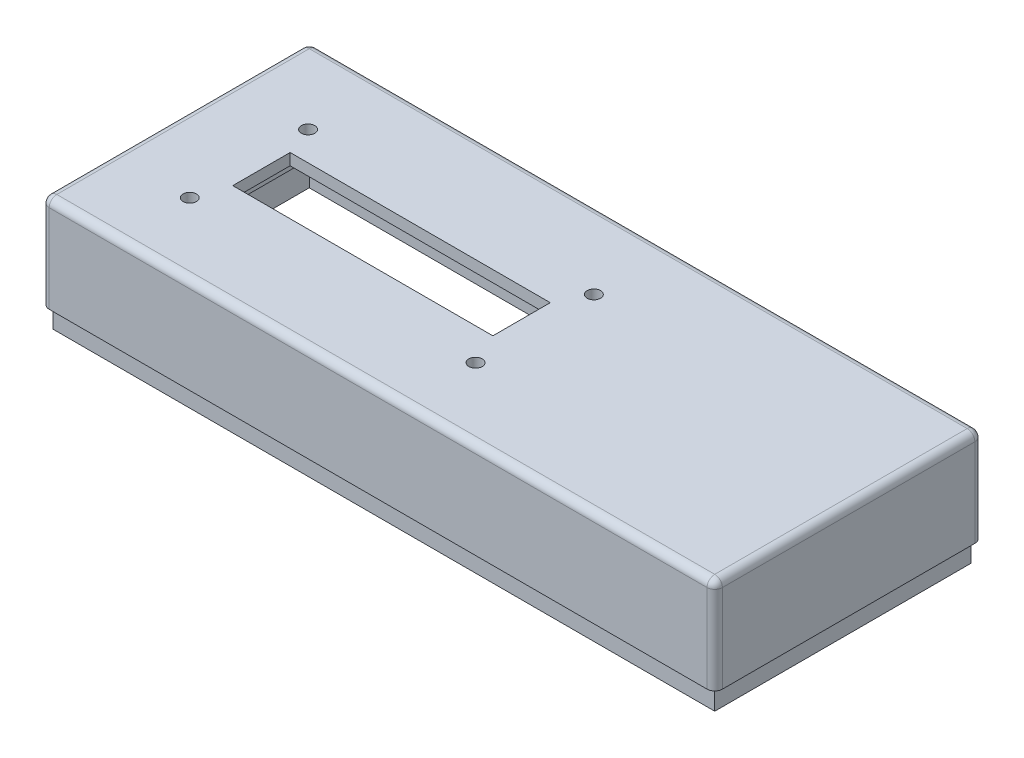
SolidWorks part; units mm, degrees
ref_plane "Front Plane" through (0, 0, 0) normal (0, 0, 1) x (1, 0, 0)
ref_plane "Top Plane" through (0, 0, 0) normal (0, 1, 0) x (1, 0, 0)
ref_plane "Right Plane" through (0, 0, 0) normal (1, 0, 0) x (0, 0, -1)
sketch "Sketch1" plane through (0, 0, 0) normal (0, 1, 0) x (1, 0, 0)
  line L1 (88, -35) -> (-88, -35)
  line L2 (88, -35) -> (88, 35)
  line L3 (88, 35) -> (-88, 35)
  line L4 (-88, -35) -> (-88, 35)
  line L5 (88, -35) -> (-88, 35) construction
  line L6 (88, 35) -> (-88, -35) construction
  point P0 (0, 0)
  dimension "D1" = 176
  dimension "D2" = 70
extrude "Boss-Extrude1" add sketch "Sketch1" along normal blind 30.5
sketch "Sketch2" plane through (0, 0, 0) normal (0, -1, 0) x (1, 0, 0)
  line L0 (-88, -35) -> (-88, 35) construction
  line L1 (85, -32) -> (-85, -32)
  line L2 (85, -32) -> (85, 32)
  line L3 (85, 32) -> (-85, 32)
  line L4 (-85, -32) -> (-85, 32)
  line L5 (85, -32) -> (-85, 32) construction
  line L6 (85, 32) -> (-85, -32) construction
  line L7 (88, -35) -> (-88, -35) construction
  line L9 (86.5, -33.5) -> (-86.5, -33.5)
  line L10 (86.5, -33.5) -> (86.5, 33.5)
  line L11 (86.5, 33.5) -> (-86.5, 33.5)
  line L12 (-86.5, -33.5) -> (-86.5, 33.5)
  line L13 (86.5, -33.5) -> (-86.5, 33.5) construction
  line L14 (86.5, 33.5) -> (-86.5, -33.5) construction
  line L15 (-88, 35) -> (88, 35)
  line L16 (-88, 35) -> (-88, -35)
  line L17 (-88, -35) -> (88, -35)
  line L18 (88, 35) -> (88, -35)
  point P0 (0, 0)
  point P10 (0, 0)
  dimension "D1" = 3
  dimension "D2" = 3
  dimension "D3" = 1.5
  dimension "D4" = 1.5
extrude "Cut-Extrude1" cut sketch "Sketch2" against normal blind 27.5 contours L4 L1 L2 L3 region at (0, 0, 0)
sketch "Sketch3" plane through (0, 0, 0) normal (0, -1, 0) x (1, 0, 0)
  line L1 (-86.5, 33.5) -> (86.5, 33.5)
  line L2 (-86.5, 33.5) -> (-86.5, -33.5)
  line L3 (-86.5, -33.5) -> (86.5, -33.5)
  line L4 (86.5, 33.5) -> (86.5, -33.5)
  line L5 (-88, 35) -> (88, 35)
  line L6 (-88, 35) -> (-88, -35)
  line L7 (-88, -35) -> (88, -35)
  line L8 (88, 35) -> (88, -35)
extrude "Cut-Extrude2" cut sketch "Sketch3" against normal blind 5.5
fillet "Fillet1" radius 2 8 edges at (-88, 30.5, 0) (0, 30.5, -35) (88, 30.5, 0) (0, 30.5, 35) (88, 18, 35) (88, 18, -35) (-88, 18, -35) (-88, 18, 35)
sketch "Sketch4" plane through (0, 27.5, 0) normal (0, -1, 0) x (1, 0, 0)
  line L0 (85, -32) -> (-85, -32) construction
  line L1 (-67, 13) -> (5, 13)
  line L2 (-67, 13) -> (-67, -12)
  line L3 (-67, -12) -> (5, -12)
  line L4 (5, 13) -> (5, -12)
  line L5 (-70, 16) -> (8, 16)
  line L6 (-70, 16) -> (-70, -15)
  line L7 (-70, -15) -> (8, -15)
  line L8 (8, 16) -> (8, -15)
  line L9 (-85, -32) -> (-85, 32) construction
  dimension "D1" = 25
  dimension "D2" = 72
  dimension "D3" = 20
  dimension "D4" = 3
  dimension "D5" = 15
  dimension "D6" = 3
  dimension "D7" = 3
  dimension "D8" = 3
extrude "Boss-Extrude2" add sketch "Sketch4" along normal blind 3
sketch "Sketch5" plane through (0, 27.5, 0) normal (0, -1, 0) x (1, 0, 0)
  line L0 (5, 13) -> (-67, 13) construction
  line L1 (-65, 8) -> (3, 8)
  line L2 (-65, 8) -> (-65, -7)
  line L3 (-65, -7) -> (3, -7)
  line L4 (3, 8) -> (3, -7)
  line L5 (-67, -12) -> (5, -12) construction
  line L6 (-67, 13) -> (-67, -12) construction
  line L7 (5, -12) -> (5, 13) construction
  dimension "D1" = 5
  dimension "D2" = 5
  dimension "D3" = 2
  dimension "D4" = 2
extrude "Cut-Extrude3" cut sketch "Sketch5" against normal up to next
sketch "Sketch6" plane through (0, 30.5, 0) normal (0, 1, 0) x (1, 0, 0)
  line L0 (3, 7) -> (3, -8) construction
  line L1 (-65, 7) -> (3, 7) construction
  circle A0 centre (-67.88, 14.57) radius 1.75
  circle A1 centre (6.83, 14.57) radius 1.75
  circle A2 centre (6.83, -16.36) radius 1.75
  circle A3 centre (-67.88, -16.36) radius 1.75
  point P8 (0, 0)
  point P9 (0, 0)
  point P10 (0, 0)
  point P11 (0, 0)
  dimension "D2" = 3.5
  dimension "D1" = 30.93
  dimension "D3" = 74.71
  dimension "D4" = 3.83
  dimension "D5" = 7.57
extrude "Cut-Extrude4" cut sketch "Sketch6" against normal up to next
